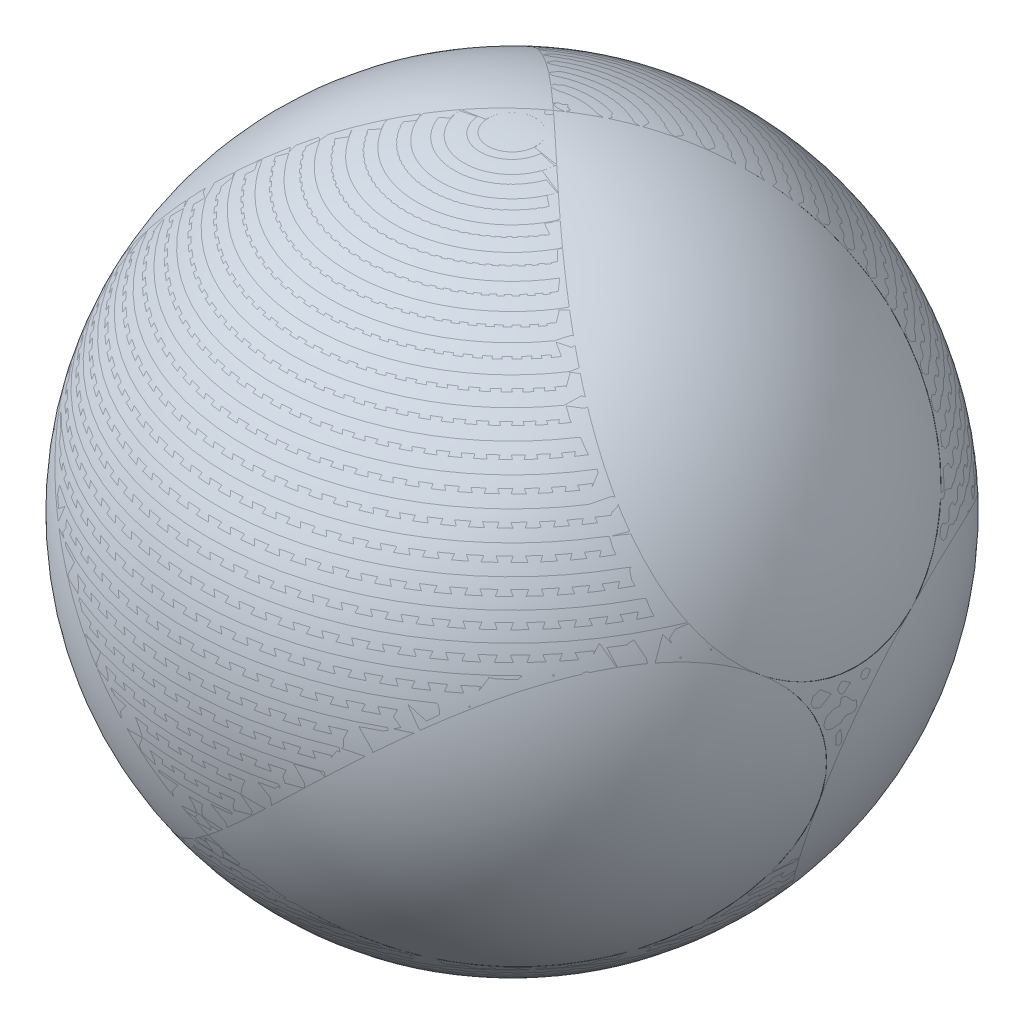
SolidWorks part; units mm, degrees
ref_plane "前视基准面" through (0, 0, 0) normal (0, 0, 1) x (1, 0, 0)
ref_plane "上视基准面" through (0, 0, 0) normal (0, 1, 0) x (1, 0, 0)
ref_plane "右视基准面" through (0, 0, 0) normal (1, 0, 0) x (0, 0, -1)
other "Configuration Table"
sketch "草图3" plane through (0, 0, 0) normal (0, 0, 1) x (1, 0, 0)
  line L0 (0, 30) -> (0, -30)
  arc A0 (0, -30) -> (0, 30) centre (0, 0) ccw
  dimension "D1" = 60
revolve "旋转11" add sketch "草图3" angle 360 about L0
sketch "草图6" plane through (0, 0, 0) normal (1, 0, 0) x (0, 0, -1)
  circle A0 centre (0, 0) radius 30
  circle A1 centre (2.0182, 15.9498) radius 13.923
  circle A2 centre (12.8038, -9.7227) radius 13.923
  circle A3 centre (-14.822, -6.2271) radius 13.923
  dimension "D1" = 60
extrude "凸台-拉伸2" add sketch "草图6" against normal up to surface and the other way up to surface separate body contours A3 A1 A0 | A2 A0 A1 | A3 A0 A2 | A3 A2 A1 region at (0, 9.0539, -21.5507) region at (0, 14.1365, 18.6163) region at (0, -23.1904, 2.9344) region at (0, 0, 0)
